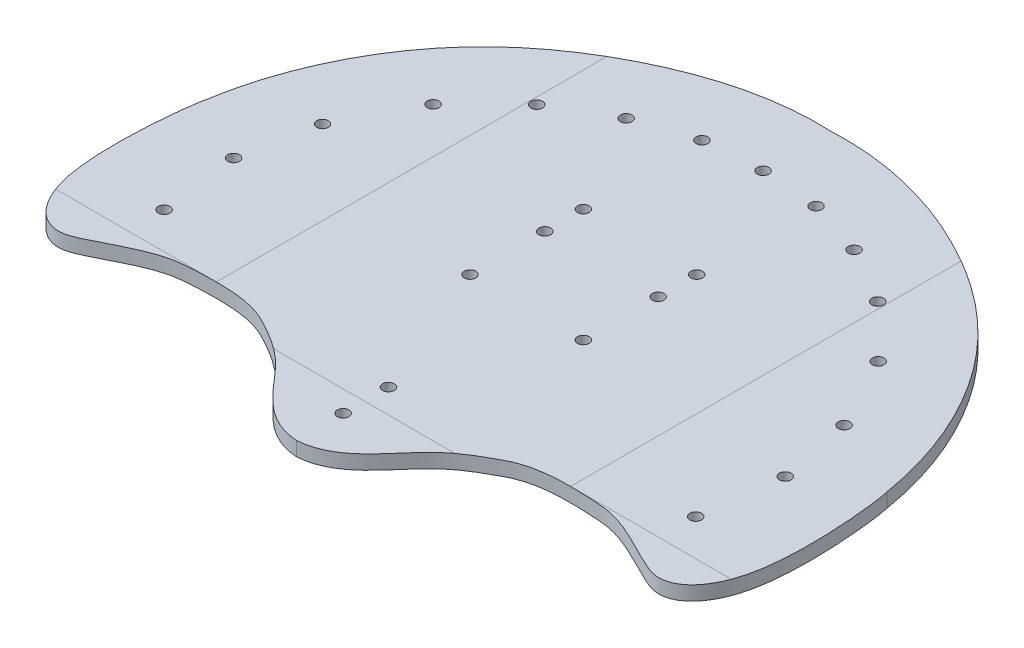
SolidWorks part; units mm, degrees
material "6061-T6 (SS)"
ref_plane "Front Plane" through (0, 0, 0) normal (0, 0, 1) x (1, 0, 0)
ref_plane "Top Plane" through (0, 0, 0) normal (0, 1, 0) x (1, 0, 0)
ref_plane "Right Plane" through (0, 0, 0) normal (1, 0, 0) x (0, 0, -1)
sketch "Sketch3" plane through (0, 0, 0) normal (0, 1, 0) x (1, 0, 0)
  line L0 (0, 0) -> (0, 159.1899) construction
  line L1 (0, 0) -> (0, -140.5301) construction
  line L2 (0, 0) -> (-190.5, 0) construction
  line L3 (0, 0) -> (190.5, 0) construction
  spline S0 degree 3 poles (-190.5, 0) (-184.3927, 37.537) (-157.2613, 93.9641) (-82.3875, 146.6227) (-31.3114, 160.7999) (0, 159.1899) knots 0 0 0 0 0.424401 0.65637 1 1 1 1
  spline S1 degree 3 poles (-190.5, 0) (-192.064, -4.9635) (-201.9672, -83.3146) (-174.6966, -109.29) (-151.6301, -100.568) (-131.4108, -87.7198) (-96.8436, -85.3754) (-78.6925, -86.2588) (-58.8335, -96.8794) (-37.3059, -109.9358) (-21.3496, -139.1148) (0, -140.5301) knots 0 0 0 0 0.166997 0.292321 0.319633 0.426735 0.458914 0.609242 0.64191 0.766802 1 1 1 1
  spline S2 degree 3 poles (190.5, 0) (192.064, -4.9635) (201.9672, -83.3146) (174.6966, -109.29) (151.6301, -100.568) (131.4108, -87.7198) (96.8436, -85.3754) (78.6925, -86.2588) (58.8335, -96.8794) (37.3059, -109.9358) (21.3496, -139.1148) (0, -140.5301) knots 0 0 0 0 0.166997 0.292321 0.319633 0.426735 0.458914 0.609242 0.64191 0.766802 1 1 1 1
  spline S3 degree 3 poles (190.5, 0) (184.3927, 37.537) (157.2613, 93.9641) (82.3875, 146.6227) (31.3114, 160.7999) (0, 159.1899) knots 0 0 0 0 0.424401 0.65637 1 1 1 1
  dimension "D1" = 381
  dimension "D2" = 299.72
  dimension "D3" = 159.1899
  dimension "D4" = 86.8953
  dimension "D5" = 104.4979
  dimension "D6" = 29.1616
  dimension "D7" = 92.2742
  dimension "D8" = 108.411
  dimension "D9" = 67.4883
  dimension "D10" = 43.7314
  dimension "D11" = 117.6915
  dimension "D12" = 162.2568
  dimension "D13" = 89.4522
  dimension "D14" = 140.1036
  dimension "D15" = 175.0666
  dimension "D16" = 50.2669
  dimension "D17" = 101.3666
  dimension "D18" = 138.1225
  dimension "D19" = 155.1557
  dimension "D20" = 192.0074
  dimension "D21" = 193.9268
  dimension "D23" = 76.6666
extrude "Boss-Extrude1" add sketch "Sketch3" along normal blind 7.9502 from surface starting at plane "Top Plane"
sketch "Sketch5" plane through (0, 0, 0) normal (0, -1, 0) x (1, 0, 0)
  line L0 (0, 0) -> (0, -20.32) construction
  line L1 (31.75, -52.07) -> (-31.75, -52.07)
  line L2 (31.75, -52.07) -> (31.75, 11.43)
  line L3 (31.75, 11.43) -> (-31.75, 11.43)
  line L4 (-31.75, -52.07) -> (-31.75, 11.43)
  line L5 (31.75, -52.07) -> (-31.75, 11.43) construction
  line L6 (31.75, 11.43) -> (-31.75, -52.07) construction
  line L7 (-31.75, -52.07) -> (-31.75, -30.48)
  line L8 (-31.75, -30.48) -> (31.75, -30.48) construction
  line L9 (0, -20.32) -> (140.7253, -20.32) construction
  line L10 (0, -20.32) -> (0, -97.1287) construction
  line L11 (0, -20.32) -> (31.9753, -118.7297) construction
  line L13 (0, -20.32) -> (63.8443, -108.1942) construction
  line L14 (0, -20.32) -> (95.5392, -89.7333) construction
  line L15 (124.7166, -60.8429) -> (0, -20.32) construction
  line L16 (0, -20.32) -> (154.5508, 21.0918) construction
  line L17 (0, -20.32) -> (148.922, 65.6601) construction
  line L18 (0, -20.32) -> (-31.9753, -118.7297) construction
  line L19 (0, -20.32) -> (-63.8443, -108.1942) construction
  line L20 (0, -20.32) -> (-95.5392, -89.7333) construction
  line L21 (-124.7166, -60.8429) -> (0, -20.32) construction
  line L22 (0, -20.32) -> (-154.5508, 21.0918) construction
  line L23 (0, -20.32) -> (-148.922, 65.6601) construction
  spline S0 degree 3 poles (-148.922, 65.6601) (-157.8584, 40.2253) (-156.2837, 8.5854) (-143.1202, -28.9506) (-139.3242, -37.3463) (-130.3709, -53.1962) (-125.215, -60.649) (-118.0488, -69.1403) (-116.5795, -70.7975) (-113.5719, -74.0252) (-112.0368, -75.592) (-107.2801, -80.2116) (-103.9215, -83.1695) (-93.3361, -91.6595) (-85.5959, -96.8074) (-76.3408, -101.9556) (-75.3049, -102.5187) (-73.219, -103.6268) (-72.1677, -104.1726) (-69.0049, -105.7765) (-66.8862, -106.8006) (-60.5068, -109.7299) (-56.2231, -111.4921) (-47.6308, -114.6027) (-43.3223, -115.9511) (-34.7104, -118.209) (-30.4072, -119.1185) (-21.8242, -120.4791) (-17.5446, -120.9304) (-11.1443, -121.2499) (-9.0138, -121.2968) (-5.8216, -121.2757) (-4.1848, -121.2414) (-2.5489, -121.1705) (-1.9677, -121.1408) (-1.9605, -121.1404) (-1.2995, -121.1064) (-0.6497, -121.073) (0, -121.0396) knots -0.292878 -0.292878 -0.292878 -0.292878 0.125 0.125 0.25 0.25 0.375 0.375 0.40625 0.40625 0.4375 0.4375 0.5 0.5 0.625 0.625 0.640625 0.640625 0.65625 0.65625 0.6875 0.6875 0.75 0.75 0.8125 0.8125 0.875 0.875 0.9375 0.9375 0.96875 0.96875 0.984375 0.992798 0.992798 0.99292 0.99292 1 1 1 1
  spline S5 degree 3 poles (998.6789, -69.6893) (665.1581, -86.8384) (331.6156, -103.9885) (-1.9268, -121.1387) (-1.9605, -121.1404) (-1.9677, -121.1408) (-2.5489, -121.1705) (-4.1848, -121.2414) (-5.8216, -121.2757) (-9.0138, -121.2968) (-11.1443, -121.2499) (-17.5446, -120.9304) (-21.8242, -120.4791) (-30.4072, -119.1185) (-34.7104, -118.209) (-43.3223, -115.9511) (-47.6308, -114.6027) (-56.2231, -111.4921) (-60.5068, -109.7299) (-66.8862, -106.8006) (-69.0049, -105.7765) (-72.1677, -104.1726) (-73.219, -103.6268) (-75.3049, -102.5187) (-76.3408, -101.9556) (-85.5959, -96.8074) (-93.3361, -91.6595) (-103.9215, -83.1695) (-107.2801, -80.2116) (-112.0368, -75.592) (-113.5719, -74.0252) (-116.5795, -70.7975) (-118.0488, -69.1403) (-125.215, -60.649) (-130.3709, -53.1962) (-139.3242, -37.3463) (-143.1202, -28.9506) (-198.5095, 128.9933) (-22.362, 351.6373) (651.8169, -587.5188) knots -3.627409 -3.627409 -3.627409 -3.627409 0.006836 0.00708 0.00708 0.007202 0.007202 0.015625 0.03125 0.03125 0.0625 0.0625 0.125 0.125 0.1875 0.1875 0.25 0.25 0.3125 0.3125 0.34375 0.34375 0.359375 0.359375 0.375 0.375 0.5 0.5 0.5625 0.5625 0.59375 0.59375 0.625 0.625 0.75 0.75 0.875 0.875 3.034324 3.034324 3.034324 3.034324 only from (0, -121.0396) to (-152.8945, 6.1184)
  spline S6 degree 3 poles (-1687.8289, -2297.0686) (-150.4269, 537.0593) (218.9922, 187.4002) (143.1202, -28.9506) (139.3242, -37.3463) (130.3709, -53.1962) (125.215, -60.649) (118.0488, -69.1403) (116.5795, -70.7975) (113.5719, -74.0252) (112.0368, -75.592) (107.2801, -80.2116) (103.9215, -83.1695) (93.3361, -91.6595) (85.5959, -96.8074) (76.3408, -101.9556) (75.3049, -102.5187) (73.219, -103.6268) (72.1677, -104.1726) (69.0049, -105.7765) (66.8862, -106.8006) (60.5068, -109.7299) (56.2231, -111.4921) (47.6308, -114.6027) (43.3223, -115.9511) (34.7104, -118.209) (30.4072, -119.1185) (21.8242, -120.4791) (17.5446, -120.9304) (11.1443, -121.2499) (9.0138, -121.2968) (5.8216, -121.2757) (4.1848, -121.2414) (2.5489, -121.1705) (1.9677, -121.1408) (1.9605, -121.1404) (-997.3522, -69.7575) (-1996.6535, -18.3753) (-2996.029, 33.0152) knots -2.879056 -2.879056 -2.879056 -2.879056 0.125 0.125 0.25 0.25 0.375 0.375 0.40625 0.40625 0.4375 0.4375 0.5 0.5 0.625 0.625 0.640625 0.640625 0.65625 0.65625 0.6875 0.6875 0.75 0.75 0.8125 0.8125 0.875 0.875 0.9375 0.9375 0.96875 0.96875 0.984375 0.992798 0.992798 0.99292 0.99292 11.881939 11.881939 11.881939 11.881939 only from (152.8945, 6.1184) to (0, -121.0396)
  spline S8 degree 3 poles (148.922, 65.6601) (157.8584, 40.2253) (156.2837, 8.5854) (143.1202, -28.9506) (139.3242, -37.3463) (130.3709, -53.1962) (125.215, -60.649) (118.0488, -69.1403) (116.5795, -70.7975) (113.5719, -74.0252) (112.0368, -75.592) (107.2801, -80.2116) (103.9215, -83.1695) (93.3361, -91.6595) (85.5959, -96.8074) (76.3408, -101.9556) (75.3049, -102.5187) (73.219, -103.6268) (72.1677, -104.1726) (69.0049, -105.7765) (66.8862, -106.8006) (60.5068, -109.7299) (56.2231, -111.4921) (47.6308, -114.6027) (43.3223, -115.9511) (34.7104, -118.209) (30.4072, -119.1185) (21.8242, -120.4791) (17.5446, -120.9304) (11.1443, -121.2499) (9.0138, -121.2968) (5.8216, -121.2757) (4.1848, -121.2414) (2.5489, -121.1705) (1.9677, -121.1408) (1.9605, -121.1404) (1.2995, -121.1064) (0.6497, -121.073) (0, -121.0396) knots -0.292878 -0.292878 -0.292878 -0.292878 0.125 0.125 0.25 0.25 0.375 0.375 0.40625 0.40625 0.4375 0.4375 0.5 0.5 0.625 0.625 0.640625 0.640625 0.65625 0.65625 0.6875 0.6875 0.75 0.75 0.8125 0.8125 0.875 0.875 0.9375 0.9375 0.96875 0.96875 0.984375 0.992798 0.992798 0.99292 0.99292 1 1 1 1
  point P0 (0, -20.32)
  point P3 (0, -20.32)
  point P14 (0, 114.3)
  point P16 (0, 88.9)
  dimension "D2" = 63.5
  dimension "D3" = 63.5
  dimension "D4" = 21.59
  dimension "D6" = 25.4
  dimension "D7" = 88.9
  dimension "D8" = 18
  dimension "D9" = 18
  dimension "D10" = 18
  dimension "D11" = 18
  dimension "D12" = 15
  dimension "D13" = 15
  dimension "D5" = 38.1
hole_wizard "F (0.257) Diameter Hole2" positions "Sketch6" profile "Sketch7" hole size "F" standard "ANSI Inch" end condition through all
sketch "Sketch6" plane through (0, 0, 0) normal (0, -1, 0) x (-1, 0, 0)
  line L0 (200000, 20.32) -> (-200140.7253, 20.32) construction
  spline S0 degree 3 poles (-148.922, -65.6601) (-157.8584, -40.2253) (-156.2837, -8.5854) (-143.1202, 28.9506) (-139.3242, 37.3463) (-130.3709, 53.1962) (-125.215, 60.649) (-118.0488, 69.1403) (-116.5795, 70.7975) (-113.5719, 74.0252) (-112.0368, 75.592) (-107.2801, 80.2116) (-103.9215, 83.1695) (-93.3361, 91.6595) (-85.5959, 96.8074) (-76.3408, 101.9556) (-75.3049, 102.5187) (-73.219, 103.6268) (-72.1677, 104.1726) (-69.0049, 105.7765) (-66.8862, 106.8006) (-60.5068, 109.7299) (-56.2231, 111.4921) (-47.6308, 114.6027) (-43.3223, 115.9511) (-34.7104, 118.209) (-30.4072, 119.1185) (-21.8242, 120.4791) (-17.5446, 120.9304) (-11.1443, 121.2499) (-9.0138, 121.2968) (-5.8216, 121.2757) (-4.1848, 121.2414) (-2.5489, 121.1705) (-1.9677, 121.1408) (-1.9605, 121.1404) (-1.2995, 121.1064) (-0.6497, 121.073) (0, 121.0396) knots -0.292878 -0.292878 -0.292878 -0.292878 0.125 0.125 0.25 0.25 0.375 0.375 0.40625 0.40625 0.4375 0.4375 0.5 0.5 0.625 0.625 0.640625 0.640625 0.65625 0.65625 0.6875 0.6875 0.75 0.75 0.8125 0.8125 0.875 0.875 0.9375 0.9375 0.96875 0.96875 0.984375 0.992798 0.992798 0.99292 0.99292 1 1 1 1 construction
  spline S1 degree 3 poles (148.922, -65.6601) (157.8584, -40.2253) (156.2837, -8.5854) (143.1202, 28.9506) (139.3242, 37.3463) (130.3709, 53.1962) (125.215, 60.649) (118.0488, 69.1403) (116.5795, 70.7975) (113.5719, 74.0252) (112.0368, 75.592) (107.2801, 80.2116) (103.9215, 83.1695) (93.3361, 91.6595) (85.5959, 96.8074) (76.3408, 101.9556) (75.3049, 102.5187) (73.219, 103.6268) (72.1677, 104.1726) (69.0049, 105.7765) (66.8862, 106.8006) (60.5068, 109.7299) (56.2231, 111.4921) (47.6308, 114.6027) (43.3223, 115.9511) (34.7104, 118.209) (30.4072, 119.1185) (21.8242, 120.4791) (17.5446, 120.9304) (11.1443, 121.2499) (9.0138, 121.2968) (5.8216, 121.2757) (4.1848, 121.2414) (2.5489, 121.1705) (1.9677, 121.1408) (1.9605, 121.1404) (1.2995, 121.1064) (0.6497, 121.073) (0, 121.0396) knots -0.292878 -0.292878 -0.292878 -0.292878 0.125 0.125 0.25 0.25 0.375 0.375 0.40625 0.40625 0.4375 0.4375 0.5 0.5 0.625 0.625 0.640625 0.640625 0.65625 0.65625 0.6875 0.6875 0.75 0.75 0.8125 0.8125 0.875 0.875 0.9375 0.9375 0.96875 0.96875 0.984375 0.992798 0.992798 0.99292 0.99292 1 1 1 1 construction
  point P3 (31.75, 52.07)
  point P6 (31.75, -11.43)
  point P9 (-31.75, -11.43)
  point P15 (31.75, 30.48)
  point P32 (-31.75, 30.48)
  point P39 (-31.75, 52.07)
  point P42 (-154.5508, -21.0918)
  point P45 (-148.922, -65.6601)
  point P48 (-146.1469, 20.32)
  point P54 (-124.7166, 60.8429)
  point P57 (-95.5392, 89.7333)
  point P60 (148.922, -65.6601)
  point P63 (154.5508, -21.0918)
  point P66 (124.7166, 60.8429)
  point P69 (95.5392, 89.7333)
  point P72 (63.8443, 108.1942)
  point P76 (31.9753, 118.7297)
  point P79 (0, 121.0396)
  point P82 (-31.9753, 118.7297)
  point P85 (-63.8443, 108.1942)
  point P88 (-95.5392, 89.7333)
  point P91 (146.1469, 20.32)
  point P95 (0, -88.9)
  point P98 (0, -114.3)
sketch "Sketch7" plane through (-31.75, 0, -52.07) normal (1, 0, 0) x (0, 0, -1)
  line L0 (0, 0) -> (0, 7.9502)
  line L1 (0, 7.9502) -> (3.2639, 7.9502)
  line L2 (3.2639, 7.9502) -> (3.2639, 0)
  line L5 (3.2639, 0) -> (0, 0)
  line L11 (0, -6.35) -> (0, 107.95) construction
  dimension "Thru Hole Dia." = 6.5278
  dimension "Thru Hole Depth" = 7.9502
sketch "Sketch9" plane through (0, 7.9502, 0) normal (0, 1, 0) x (1, 0, 0)
  line L0 (99.2548, -86.0492) -> (99.2548, 132.7681)
  line L1 (-50.7649, -102.4301) -> (50.7649, -102.4301)
  line L2 (0, 0) -> (0, 108.4804) construction
  line L3 (194.5048, -47.9492) -> (99.2548, -47.9492) construction
  line L4 (148.922, -65.6601) -> (193.6656, -65.6601) construction
  line L5 (-99.2548, -86.0492) -> (-99.2548, 132.7681)
  line L6 (99.2548, -86.0492) -> (189.3138, -86.0492)
  line L7 (-99.2548, -86.0492) -> (-189.3138, -86.0492)
  spline S0 degree 3 poles (0, -140.5301) (21.3496, -139.1148) (37.3059, -109.9358) (58.8335, -96.8794) (78.6925, -86.2588) (96.8436, -85.3754) (131.4108, -87.7198) (151.6301, -100.568) (174.6966, -109.29) (201.9672, -83.3146) (192.064, -4.9635) (190.5, 0) knots 0 0 0 0 0.233198 0.35809 0.390758 0.541086 0.573265 0.680367 0.707679 0.833003 1 1 1 1 construction
  spline S1 degree 3 poles (190.5, 0) (184.3927, 37.537) (157.2613, 93.9641) (82.3875, 146.6227) (31.3114, 160.7999) (0, 159.1899) knots 0 0 0 0 0.424401 0.65637 1 1 1 1 construction
  spline S2 degree 3 poles (-190.5, 0) (-192.064, -4.9635) (-201.9672, -83.3146) (-174.6966, -109.29) (-151.6301, -100.568) (-131.4108, -87.7198) (-96.8436, -85.3754) (-78.6925, -86.2588) (-58.8335, -96.8794) (-37.3059, -109.9358) (-21.3496, -139.1148) (0, -140.5301) knots 0 0 0 0 0.166997 0.292321 0.319633 0.426735 0.458914 0.609242 0.64191 0.766802 1 1 1 1 construction
  point P21 (171.0944, -65.6601)
  dimension "D1" = 38.1
  dimension "D2" = 95.25
  dimension "D3" = 38.1
split line "Split Line1"
sketch "Sketch10" plane through (0, 0, 0) normal (0, -1, 0) x (1, 0, 0)
  line L0 (31.75, 11.43) -> (31.75, 24.13) construction
  line L1 (-31.75, 11.43) -> (31.75, 11.43) construction
  line L2 (-31.75, 11.43) -> (-31.75, -52.07) construction
  line L3 (-31.75, -52.07) -> (31.75, -52.07) construction
  line L4 (31.75, 11.43) -> (31.75, -52.07) construction
  line L5 (-44.45, 24.13) -> (44.45, 24.13)
  line L6 (-44.45, 24.13) -> (-44.45, -64.77)
  line L7 (-44.45, -64.77) -> (44.45, -64.77)
  line L8 (44.45, 24.13) -> (44.45, -64.77)
  line L9 (31.75, 11.43) -> (44.45, 11.43) construction
  line L10 (-31.75, -52.07) -> (-44.45, -52.07) construction
  line L11 (-31.75, -52.07) -> (-31.75, -64.77) construction
  dimension "D1" = 88.9
split line "Split Line2"
equation "\"Plate thickness\"=0.313"
equation "\"D1@Boss-Extrude1\"=\"Plate thickness\""
equation "\"Bracket Alignment\"= .80"
equation "\"D1@Sketch5\"=\"Bracket Alignment\""
